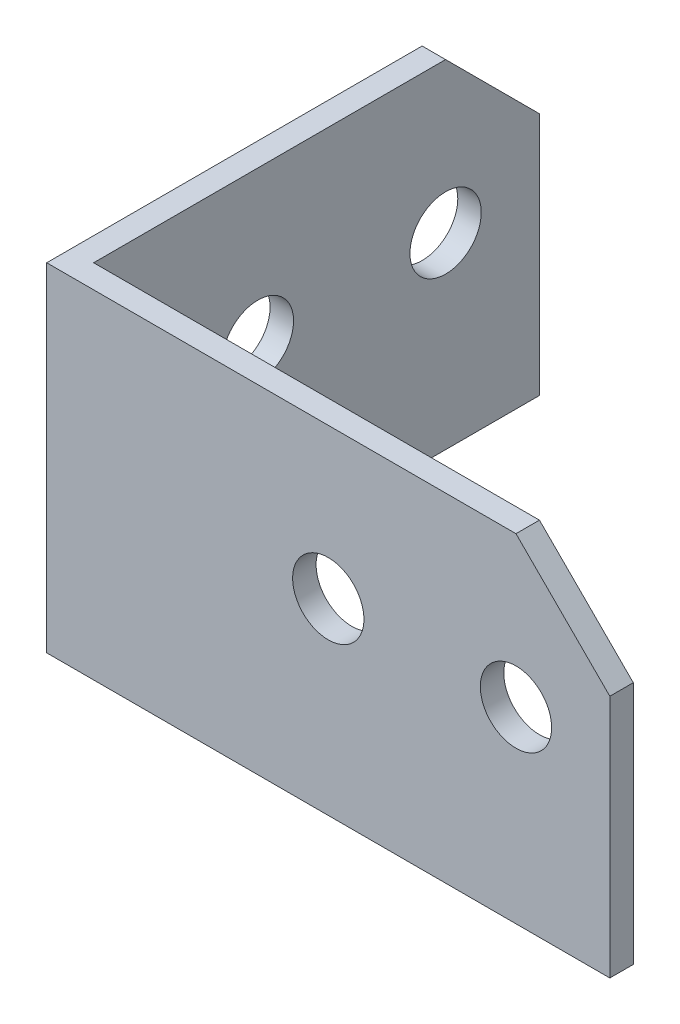
SolidWorks part; units mm, degrees
material "6061-T6 (SS)"
ref_plane "Front Plane" through (0, 0, 0) normal (0, 0, 1) x (1, 0, 0)
ref_plane "Top Plane" through (0, 0, 0) normal (0, 1, 0) x (1, 0, 0)
ref_plane "Right Plane" through (0, 0, 0) normal (1, 0, 0) x (0, 0, -1)
sketch "Sketch1" plane through (0, 0, 0) normal (0, 1, 0) x (1, 0, 0)
  line L1 (-18.1093, 25.3412) -> (-16.5218, 25.3412)
  line L2 (-18.1093, 25.3412) -> (-18.1093, -6.4088)
  line L4 (-16.5218, 25.3412) -> (-16.5218, -4.8213)
  line L5 (-18.1093, -6.4088) -> (19.9907, -6.4088)
  line L7 (-16.5218, -4.8213) -> (19.9907, -4.8213)
  line L8 (19.9907, -6.4088) -> (19.9907, -4.8213)
  dimension "D1" = 1.5875
  dimension "D2" = 1.5875
  dimension "D3" = 31.75
  dimension "D4" = 38.1
extrude "Boss-Extrude1" add sketch "Sketch1" along normal blind 45.72 contours L2 L5 L8 L7 L4 L1
sketch "Sketch2" plane through (0, 0, 4.8213) normal (0, 0, -1) x (-1, 0, 0)
  line L1 (-13.6407, 35.56) -> (-0.9407, 35.56) construction
  line L2 (-13.6407, 35.56) -> (-13.6407, 10.16) construction
  line L3 (-13.6407, 10.16) -> (-0.9407, 10.16) construction
  line L4 (-0.9407, 35.56) -> (-0.9407, 10.16) construction
  line L5 (18.1093, 45.72) -> (18.1093, 0) construction
  line L6 (16.5218, 45.72) -> (-19.9907, 45.72) construction
  circle A0 centre (-0.9407, 35.56) radius 2.413
  circle A1 centre (-13.6407, 35.56) radius 2.413
  circle A2 centre (-13.6407, 10.16) radius 2.413
  circle A3 centre (-0.9407, 10.16) radius 2.413
  dimension "D5" = 4.826
  dimension "D1" = 12.7
  dimension "D2" = 19.05
  dimension "D3" = 10.16
  dimension "D4" = 25.4
extrude "Cut-Extrude1" cut sketch "Sketch2" against normal through all
sketch "Sketch3" plane through (-16.5218, 0, 0) normal (1, 0, 0) x (0, 0, -1)
  line L0 (-6.4088, 45.72) -> (-6.4088, 0) construction
  line L1 (18.9912, 35.56) -> (6.2912, 35.56) construction
  line L2 (18.9912, 35.56) -> (18.9912, 10.16) construction
  line L3 (18.9912, 10.16) -> (6.2912, 10.16) construction
  line L4 (6.2912, 35.56) -> (6.2912, 10.16) construction
  line L5 (25.3412, 45.72) -> (-4.8213, 45.72) construction
  circle A0 centre (6.2912, 35.56) radius 2.413
  circle A1 centre (18.9912, 35.56) radius 2.413
  circle A2 centre (18.9912, 10.16) radius 2.413
  circle A3 centre (6.2912, 10.16) radius 2.413
  dimension "D5" = 4.826
  dimension "D1" = 12.7
  dimension "D2" = 25.4
  dimension "D3" = 10.16
  dimension "D4" = 12.7
extrude "Cut-Extrude2" cut sketch "Sketch3" against normal through all
chamfer "Chamfer1" distance 6.35 angle 45 4 edges at (19.9907, 45.72, 5.615) (19.9907, 0, 5.615) (-17.3155, 0, -25.3412) (-17.3155, 45.72, -25.3412)
sketch "Sketch4" plane through (0, 0, 4.8213) normal (0, 0, -1) x (-1, 0, 0)
  line L0 (-19.9907, 22.86) -> (16.5218, 22.86)
  line L1 (-19.9907, 39.37) -> (-19.9907, 6.35) construction
  line L2 (16.5218, 45.72) -> (16.5218, 0) construction
  line L3 (16.5218, 22.86) -> (16.5218, 0)
  line L4 (16.5218, 0) -> (-13.6407, 0)
  line L5 (-13.6407, 0) -> (-19.9907, 6.35)
  line L6 (-19.9907, 6.35) -> (-19.9907, 22.86)
sketch "Sketch5" plane through (-16.5218, 0, 0) normal (1, 0, 0) x (0, 0, -1)
  line L0 (25.3412, 22.86) -> (-4.8213, 22.86)
  line L1 (25.3412, 39.37) -> (25.3412, 6.35) construction
  line L2 (-4.8213, 22.86) -> (-4.8213, 0)
  line L3 (-4.8213, 0) -> (18.9912, 0)
  line L4 (18.9912, 0) -> (25.3412, 6.35)
  line L5 (25.3412, 6.35) -> (25.3412, 22.86)
extrude "Cut-Extrude3" cut sketch "Sketch4" against normal through all
extrude "Cut-Extrude4" cut sketch "Sketch5" against normal through all
sketch "Sketch6" plane through (0, 0, 6.4088) normal (0, 0, 1) x (1, 0, 0)
  line L0 (-18.1093, 45.72) -> (-18.1093, 0) construction
  line L1 (-18.1093, 22.86) -> (-16.5218, 22.86)
  line L2 (-18.1093, 22.86) -> (-18.1093, 0)
  line L3 (-18.1093, 0) -> (-16.5218, 0)
  line L4 (-16.5218, 22.86) -> (-16.5218, 0)
extrude "Cut-Extrude5" cut sketch "Sketch6" against normal through all
